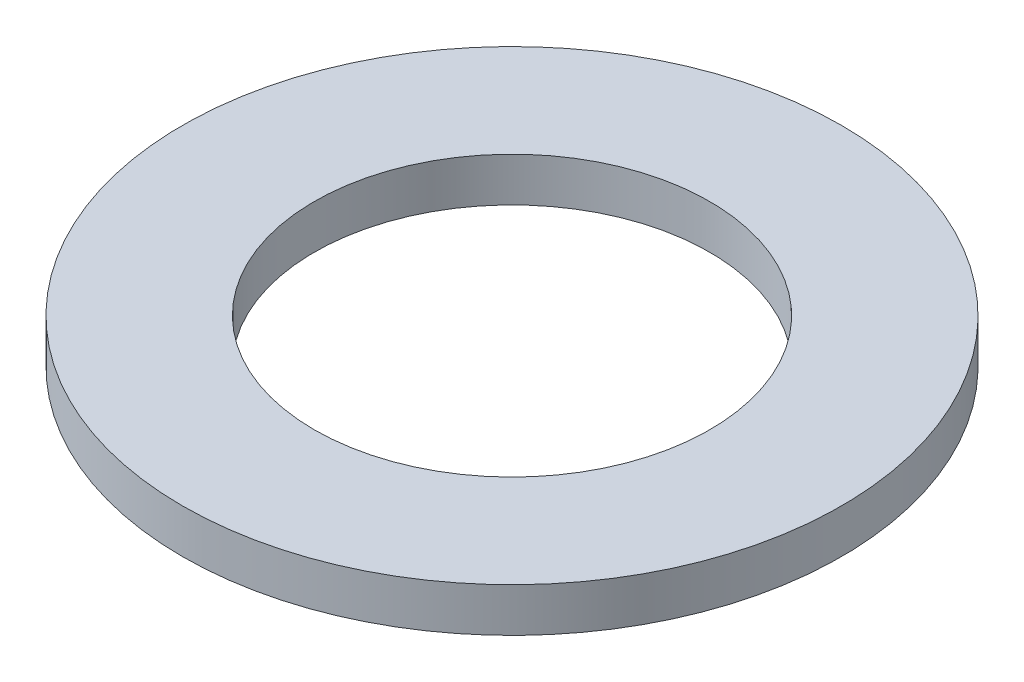
SolidWorks part; units mm, degrees
ref_plane "Front Plane" through (0, 0, 0) normal (0, 0, 1) x (1, 0, 0)
ref_plane "Top Plane" through (0, 0, 0) normal (0, 1, 0) x (1, 0, 0)
ref_plane "Right Plane" through (0, 0, 0) normal (1, 0, 0) x (0, 0, -1)
sketch "Sketch1" plane through (0, 0, 0) normal (0, 1, 0) x (1, 0, 0)
  circle A0 centre (0, 0) radius 75
  dimension "FLANGE_OD" = 150
extrude "Boss-Extrude1" add sketch "Sketch1" along normal blind 10
sketch "Sketch2" plane through (0, 0, 0) normal (0, 1, 0) x (1, 0, 0)
  circle A0 centre (0, 0) radius 45
  dimension "BORE_D" = 90
extrude "Cut-Extrude1" cut sketch "Sketch2" along normal through all
sketch "Sketch3" plane through (0, 10, 0) normal (0, 1, 0) x (1, 0, 0)
  circle A0 centre (0, 0) radius 27.2225 construction
  circle A1 centre (-27.2225, 0) radius 1.6922
  dimension "BOLT_D" = 3.3843
  dimension "BOLT_PCD" = 54.445
extrude "Cut-Extrude2" cut sketch "Sketch3" against normal blind 6.0579 rebuild error yes
pattern_circular "CirPattern1" count 5 over 360 rebuild error yes
